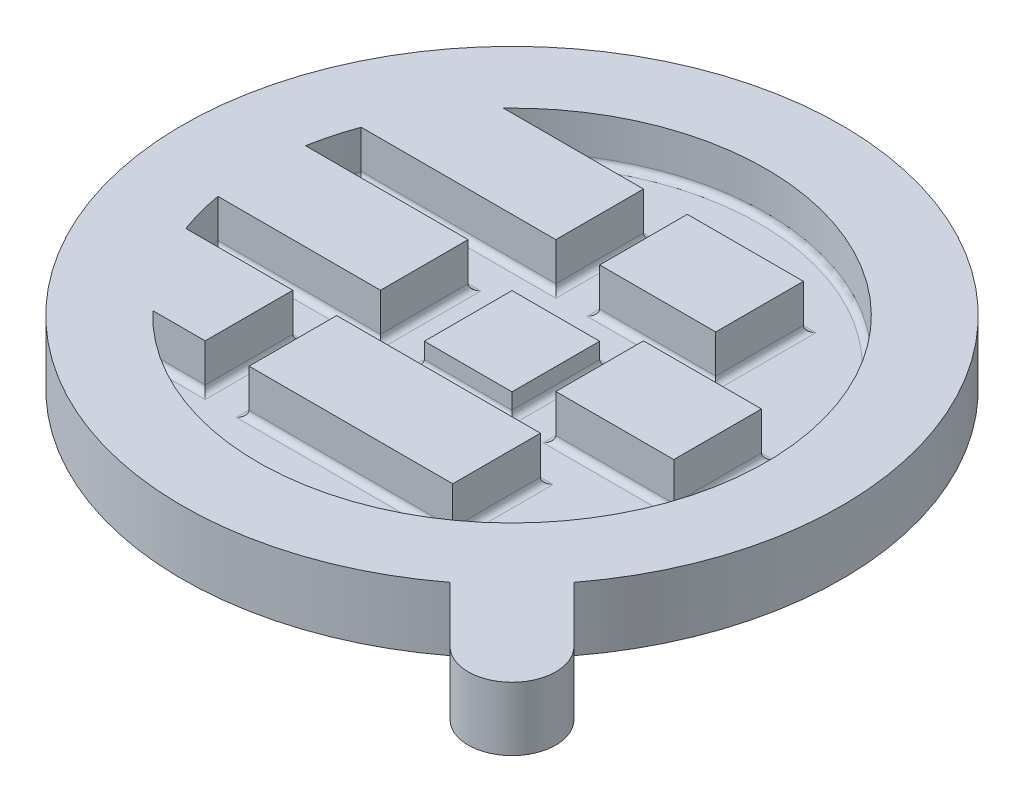
SolidWorks part; units mm, degrees
ref_plane "Front Plane" through (0, 0, 0) normal (0, 0, 1) x (1, 0, 0)
ref_plane "Top Plane" through (0, 0, 0) normal (0, 1, 0) x (1, 0, 0)
ref_plane "Right Plane" through (0, 0, 0) normal (1, 0, 0) x (0, 0, -1)
sketch "Sketch1" plane through (0, 0, 0) normal (0, 1, 0) x (1, 0, 0)
  line L0 (100, 100) -> (0, 0) construction
  line L1 (0, 0) -> (100, 0) construction
  line L2 (0, 0) -> (0, 100) construction
  line L3 (0, 100) -> (100, 100) construction
  line L5 (0, 100) -> (100, 0) construction
  line L6 (100, 9.7581) -> (78.7868, 30.9713)
  line L7 (90.2419, 0) -> (69.0287, 21.2132)
  line L8 (100, 9.7581) -> (90.2419, 0)
  line L9 (78.7868, 30.9713) -> (69.0287, 21.2132) construction
  line L10 (50, 50) -> (0, 50) construction
  line L11 (43.1, 56.9) -> (56.9, 56.9)
  line L12 (43.1, 56.9) -> (43.1, 43.1)
  line L13 (43.1, 43.1) -> (56.9, 43.1)
  line L14 (56.9, 56.9) -> (56.9, 43.1)
  line L15 (43.1, 56.9) -> (56.9, 43.1) construction
  line L16 (43.1, 43.1) -> (56.9, 56.9) construction
  line L17 (70.7, 29.3) -> (0, 29.3) construction
  line L18 (10, 56.9) -> (36.2, 56.9)
  line L19 (10, 56.9) -> (10, 43.1)
  line L20 (10, 43.1) -> (36.2, 43.1)
  line L21 (36.2, 56.9) -> (36.2, 43.1)
  line L22 (10, 56.9) -> (36.2, 43.1) construction
  line L23 (10, 43.1) -> (36.2, 56.9) construction
  line L24 (70.7, 70.7) -> (0, 70.7) construction
  line L25 (50, 50) -> (50, 100) construction
  line L26 (12.4559, 77.6) -> (43.1, 77.6)
  line L27 (12.4559, 77.6) -> (12.4559, 63.8)
  line L28 (12.4559, 63.8) -> (43.1, 63.8)
  line L29 (43.1, 77.6) -> (43.1, 63.8)
  line L30 (12.4559, 77.6) -> (43.1, 63.8) construction
  line L31 (12.4559, 63.8) -> (43.1, 77.6) construction
  line L32 (50, 50) -> (100, 50) construction
  line L33 (50, 77.6) -> (68.27, 77.6)
  line L34 (50, 77.6) -> (50, 63.8)
  line L35 (50, 63.8) -> (68.27, 63.8)
  line L36 (68.27, 77.6) -> (68.27, 63.8)
  line L37 (50, 77.6) -> (68.27, 63.8) construction
  line L38 (50, 63.8) -> (68.27, 77.6) construction
  line L40 (63.8, 56.9) -> (82.37, 56.9)
  line L41 (63.8, 56.9) -> (63.8, 43.1)
  line L42 (63.8, 43.1) -> (82.37, 43.1)
  line L43 (82.37, 56.9) -> (82.37, 43.1)
  line L44 (63.8, 56.9) -> (82.37, 43.1) construction
  line L45 (63.8, 43.1) -> (82.37, 56.9) construction
  line L46 (12.4559, 36.2) -> (29.3, 36.2)
  line L47 (12.4559, 36.2) -> (12.4559, 22.4)
  line L48 (12.4559, 22.4) -> (29.3, 22.4)
  line L49 (29.3, 36.2) -> (29.3, 22.4)
  line L50 (12.4559, 36.2) -> (29.3, 22.4) construction
  line L51 (12.4559, 22.4) -> (29.3, 36.2) construction
  line L52 (36.2, 36.2) -> (68.27, 36.2)
  line L53 (36.2, 36.2) -> (36.2, 22.4)
  line L54 (36.2, 22.4) -> (68.27, 22.4)
  line L55 (68.27, 36.2) -> (68.27, 22.4)
  line L56 (36.2, 36.2) -> (68.27, 22.4) construction
  line L57 (36.2, 22.4) -> (68.27, 36.2) construction
  circle A0 centre (50, 50) radius 50
  arc A1 (100, 9.7581) -> (90.2419, 0) centre (95.121, 4.879) cw
  circle A2 centre (50, 50) radius 40
  circle A3 centre (68.27, 77.6) radius 6.9009 construction
  circle A4 centre (82.37, 56.9) radius 6.9028 construction
  circle A5 centre (68.27, 22.4) radius 6.9009 construction
  circle A6 centre (50, 50) radius 51.9
  point P19 (23.1, 50)
  point P29 (27.7779, 70.7)
  point P34 (59.135, 70.7)
  point P40 (73.085, 50)
  point P46 (20.8779, 29.3)
  point P52 (52.235, 29.3)
  dimension "D5" = 30
  dimension "D12" = 20.7
  dimension "D24" = 6.9009
  dimension "D25" = 6.9028
  dimension "D27" = 11.9
  dimension "D1" = 100
  dimension "D2" = 100
  dimension "D3" = 6.9
  dimension "D4" = 6.9
  dimension "D7" = 13.8
  dimension "D8" = 13.8
  dimension "D9" = 13.8
  dimension "D10" = 26.2
  dimension "D11" = 6.9
  dimension "D13" = 20.7
  dimension "D14" = 13.8
  dimension "D15" = 13.8
  dimension "D16" = 18.27
  dimension "D17" = 6.9
  dimension "D18" = 13.8
  dimension "D19" = 6.9
  dimension "D20" = 18.57
  dimension "D21" = 13.8
  dimension "D22" = 6.9
  dimension "D23" = 13.8
  dimension "D26" = 6.9009
  dimension "D6" = 10
extrude "Boss-Extrude12" add sketch "Sketch1" along normal blind 3 contours A2 L18 L19 | A2 L19 L20 | A2 L27 L26 L6 A0 L7 L48 L47 L20 L19 L18 | A2 L26 L27 | L18 A2 L20 L21 | L46 A2 L48 L49 | A2 L47 L48 | L26 A2 L28 L29 | L36 L33 L34 L35 | L43 L40 L41 L42 | L14 L11 L12 L13 | L55 L52 L53 L54 | A2 L7 A0 L6 | A0 L7 L8 L6 | A1 L8 | L28 A2 L18 L21 L20 L46 L49 L48 L26 L29 L52 L55 L54 L53 L40 L43 L42 L41 L33 L36 L35 L34 L11 L14 L13 L12 | L6 A6 L7 A0 | L7 A6 L6 A0 region at (90.8552, 0, -9.1448) region at (97.1917, 0, -2.8083) region at (85.9163, 0, -14.0837) region at (91.6121, 0, -20.222) region at (81.6927, 0, -18.3073) region at (87.3177, 0, -24.4404) region at (77.4873, 0, -22.5127) region at (22.4668, 0, -30.0395) region at (15.1126, 0, -26.6168) region at (15.1126, 0, -73.3832) region at (29.4847, 0, -70.3384) region at (23.199, 0, -50) region at (10.1797, 0, -44.8224) region at (10.1797, 0, -55.1776) region at (50, 0, -50) region at (59.135, 0, -70.7) region at (73.085, 0, -50) region at (52.235, 0, -29.3)
extrude "Boss-Extrude13" add sketch "Sketch1<16>" along normal blind 10 contours A2 L27 L26 L6 A0 L7 L48 L47 L20 L19 L18 | A2 L26 L27 | A2 L18 L19 | A2 L19 L20 | L18 A2 L20 L21 | L26 A2 L28 L29 | L36 L33 L34 L35 | L46 A2 L48 L49 | A2 L47 L48 | L55 L52 L53 L54 | L43 L40 L41 L42 | A2 L7 A0 L6 | A0 L7 L8 L6 | A1 L8 | L6 A6 L7 A0 | L7 A6 L6 A0 region at (90.8552, 0, -9.1448) region at (97.1917, 0, -2.8083) region at (85.9163, 0, -14.0837) region at (91.6121, 0, -20.222) region at (81.6927, 0, -18.3073) region at (87.3177, 0, -24.4404) region at (22.4668, 0, -30.0395) region at (15.1126, 0, -26.6168) region at (15.1126, 0, -73.3832) region at (29.4847, 0, -70.3384) region at (23.199, 0, -50) region at (10.1797, 0, -44.8224) region at (10.1797, 0, -55.1776) region at (59.135, 0, -70.7) region at (73.085, 0, -50) region at (52.235, 0, -29.3)
sketch "Sketch1<16>" plane through (0, 0, 0) normal (0, 1, 0) x (1, 0, 0) same geometry as "Sketch1"
extrude "Boss-Extrude14" add sketch "Sketch1<17>" along normal blind 6.5 contours L11 L14 L13 L12
sketch "Sketch1<17>" plane through (0, 0, 0) normal (0, 1, 0) x (1, 0, 0) same geometry as "Sketch1"
fillet "Fillet1" radius 1 28 edges at (90, 3, -50) (36.2, 3, -29.3) (52.235, 3, -22.4) (50, 3, -70.7) (59.135, 3, -63.8) (43.1, 3, -50) (50, 3, -43.1) (63.8, 3, -50) (73.085, 3, -43.1) (50, 3, -56.9) (73.085, 3, -56.9) (56.9, 3, -50) (52.235, 3, -36.2) (68.27, 3, -29.3) (82.37, 3, -50) (68.27, 3, -70.7) (59.135, 3, -77.6) (32.0738, 3, -77.6) (43.1, 3, -70.7) (27.7779, 3, -63.8) (11.3734, 3, -60.3915) (23.3998, 3, -56.9) (36.2, 3, -50) (23.3998, 3, -43.1) (11.3734, 3, -39.6085) (20.8779, 3, -36.2) (29.3, 3, -29.3) (25.1738, 3, -22.4)
